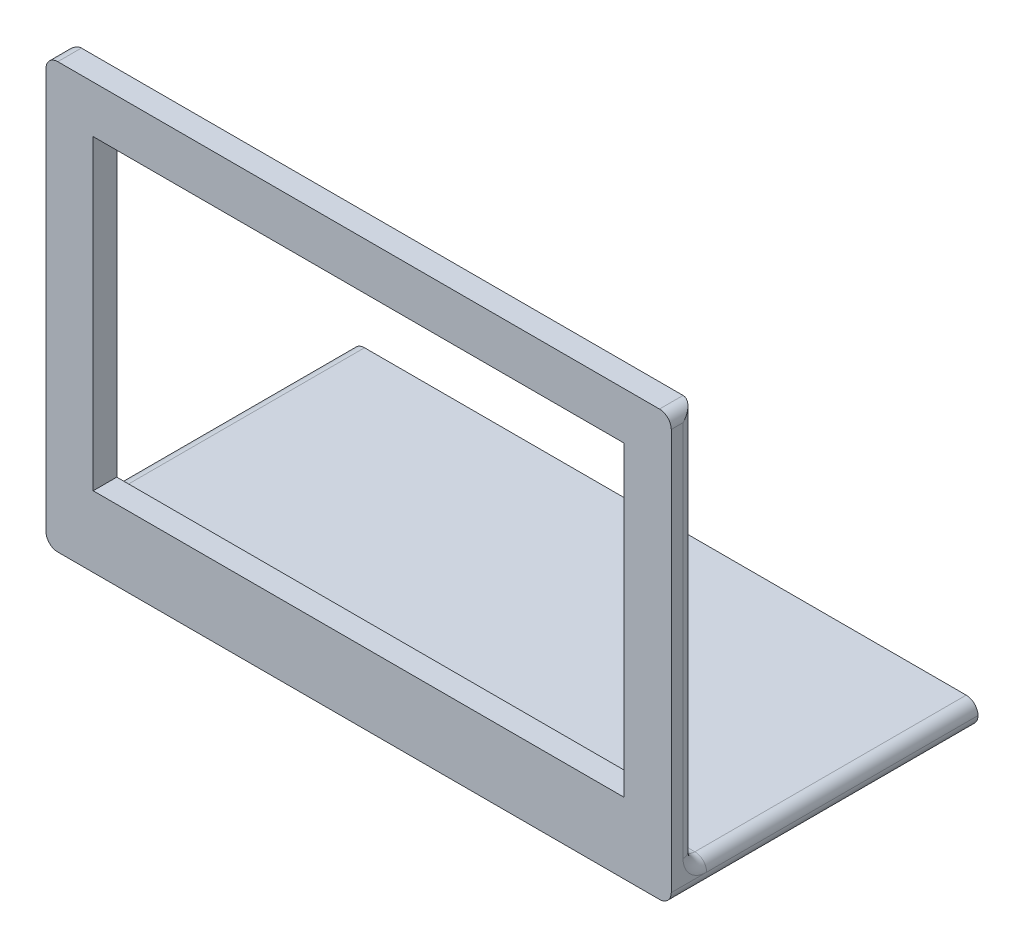
SolidWorks part; units mm, degrees
ref_plane "Front Plane" through (0, 0, 0) normal (0, 0, 1) x (1, 0, 0)
ref_plane "Top Plane" through (0, 0, 0) normal (0, 1, 0) x (1, 0, 0)
ref_plane "Right Plane" through (0, 0, 0) normal (1, 0, 0) x (0, 0, -1)
sketch "Sketch1" plane through (0, 0, 0) normal (0, 0, 1) x (1, 0, 0)
  line L0 (-24.7837, 30.7231) -> (-28.7837, 30.7231) construction
  line L1 (-24.7837, 46.8354) -> (20.2163, 46.8354)
  line L2 (-24.7837, 46.8354) -> (-24.7837, 20.8354)
  line L3 (-24.7837, 20.8354) -> (20.2163, 20.8354)
  line L4 (20.2163, 46.8354) -> (20.2163, 20.8354)
  line L7 (-28.7837, 50.8354) -> (24.2163, 50.8354)
  line L8 (-28.7837, 50.8354) -> (-28.7837, 16.8354)
  line L9 (-28.7837, 16.8354) -> (24.2163, 16.8354)
  line L10 (24.2163, 50.8354) -> (24.2163, 16.8354)
  line L11 (24.2163, 16.8354) -> (24.2163, 14.8354)
  line L13 (-2.2837, 20.8354) -> (-2.2837, 16.8354) construction
  line L14 (20.2163, 38.5557) -> (24.2163, 38.5557) construction
  line L15 (-14.9242, 46.8354) -> (-14.9242, 50.8354) construction
  line L17 (24.2163, 14.8354) -> (-28.7837, 14.8354)
  line L18 (-28.7837, 14.8354) -> (-28.7837, 16.8354)
  point P0 (0, 0)
  dimension "D1" = 45
  dimension "D2" = 26
  dimension "D3" = 2
  dimension "D4" = 4
extrude "Boss-Extrude1" add sketch "Sketch1" along normal blind 2 contours L18 L17 L11 L9 | L10 L7 L8 L9 L1 L4 L3 L2 region at (-2.2837, 50.2057, 0) region at (-2.2837, 15.8354, 0)
extrude "Boss-Extrude4" add sketch "Sketch1<5>" against normal blind 24 contours L18 L17 L11 L9 region at (-2.2837, 15.8354, 0)
sketch "Sketch1<5>" plane through (0, 0, 0) normal (0, 0, 1) x (1, 0, 0) same geometry as "Sketch1"
fillet "Fillet2" radius 1 9 edges at (-28.7837, 33.8354, 0) (24.2163, 33.8354, 0) (-2.2837, 16.8354, 0) (-28.7837, 16.8354, -12) (24.2163, 16.8354, -12) (24.2163, 50.8354, 1) (24.2163, 14.8354, -11) (-28.7837, 50.8354, 1) (-28.7837, 14.8354, -11)
